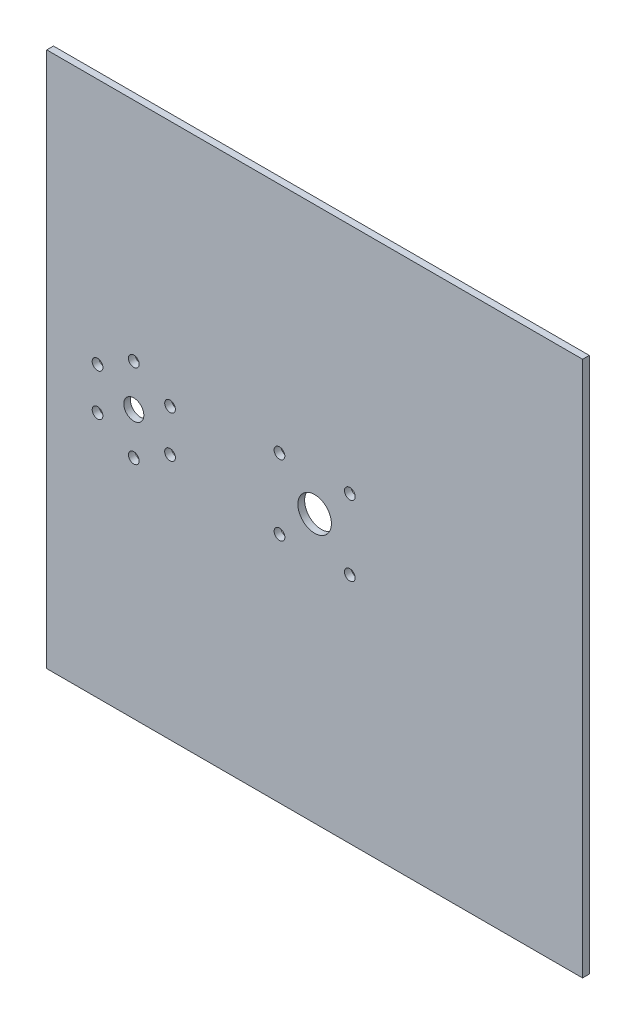
SolidWorks part; units mm, degrees
ref_plane "Front Plane" through (0, 0, 0) normal (0, 0, 1) x (1, 0, 0)
ref_plane "Top Plane" through (0, 0, 0) normal (0, 1, 0) x (1, 0, 0)
ref_plane "Right Plane" through (0, 0, 0) normal (1, 0, 0) x (0, 0, -1)
sketch "Sketch1" plane through (0, 0, 0) normal (0, 0, 1) x (1, 0, 0)
  line L1 (-80, 80) -> (80, 80)
  line L2 (-80, 80) -> (-80, -80)
  line L3 (-80, -80) -> (80, -80)
  line L4 (80, 80) -> (80, -80)
  dimension "D1" = 80
  dimension "D2" = 80
  dimension "D3" = 80
  dimension "D4" = 80
extrude "Boss-Extrude1" add sketch "Sketch1" along normal blind 2
sketch "Sketch2" plane through (0, 0, 2) normal (0, 0, 1) x (1, 0, 0)
  line L0 (0, 80) -> (0, -80) construction
  line L1 (80, 80) -> (-80, 80) construction
  line L2 (-80, -80) -> (80, -80) construction
  line L3 (80, 0) -> (-80, 0) construction
  line L4 (80, -80) -> (80, 80) construction
  line L5 (-80, 80) -> (-80, -80) construction
  circle A0 centre (0, 0) radius 5
extrude "Cut-Extrude1" cut sketch "Sketch2" against normal blind 2
ref_axis "Axis1" through (0, 0, 0) along (0, 0, 1)
sketch "Sketch5" plane through (0, 0, 0) normal (0, 0, -1) x (-1, 0, 0)
  circle A0 centre (10.5, 10.5) radius 1.6
  circle A1 centre (10.5, -10.5) radius 1.6
  circle A2 centre (-10.5, -10.5) radius 1.6
  circle A3 centre (-10.5, 10.5) radius 1.6
  point P12 (0, 0)
  dimension "D1" = 4
extrude "Cut-Extrude3" cut sketch "Sketch5" against normal blind 2
sketch "Sketch8" plane through (0, 0, 0) normal (0, 0, -1) x (-1, 0, 0)
  line L0 (54, 0) -> (54, 12.5) construction
  circle A0 centre (54, 0) radius 3
  circle A1 centre (54, 12.5) radius 1.6
  circle A2 centre (64.8253, 6.25) radius 1.6
  circle A3 centre (64.8253, -6.25) radius 1.6
  circle A4 centre (54, -12.5) radius 1.6
  circle A5 centre (43.1747, -6.25) radius 1.6
  circle A6 centre (43.1747, 6.25) radius 1.6
  point P17 (54, 0)
  dimension "D1" = 6
extrude "Cut-Extrude5" cut sketch "Sketch8" against normal blind 2
